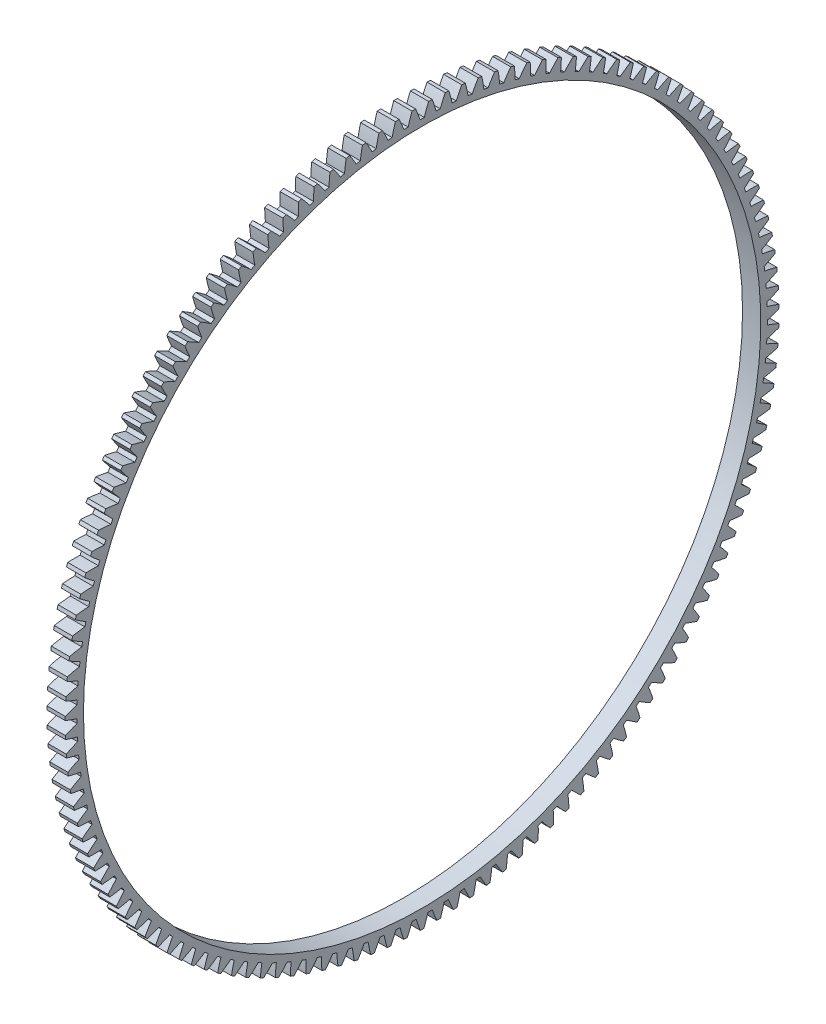
SolidWorks part; units mm, degrees
ref_plane "Plane1" through (0, 0, 0) normal (0, 0, 1) x (1, 0, 0)
ref_plane "Plane2" through (0, 0, 0) normal (0, 1, 0) x (1, 0, 0)
ref_plane "Plane3" through (0, 0, 0) normal (1, 0, 0) x (0, 0, -1)
sketch "HoldingSke" plane through (0, 0, 0) normal (0, 1, 0) x (1, 0, 0)
  line L0 (0, 0) -> (-0.3536, -0.3536)
  line L1 (-15, 0) -> (100, 0) construction
  line L2 (0, 0) -> (-2.1039, 2.3779)
  line L3 (0, 0) -> (-11.863, 4.5341)
  line L4 (0, 0) -> (-6.1066, 6.1066)
  line L5 (0, 0) -> (-46.8476, -17.4728)
  line L6 (0, 0) -> (-7.4607, -5.0337)
  line L7 (-2.1039, 2.3779) -> (8.6586, 51.2059)
  line L8 (-76.2, 54.61) -> (-63.8, 54.61)
  line L9 (-71.009, 38.7566) -> (-53.1078, 45.2721)
  line L10 (-76.2, 71.12) -> (104.1128, 71.12)
  line L11 (0, 0) -> (-9, 0)
  line L12 (-76.2, 101.6) -> (-76.133, 101.6)
  line L13 (24.9733, 27.94) -> (52.9518, 28.4284)
  line L14 (24.9733, 27.94) -> (24.9743, 27.94)
  line L15 (24.9733, 27.94) -> (100.4006, 29.5858)
  line L16 (-63.627, -2) -> (-12.827, -2)
  circle A0 centre (0, 0) radius 130
  circle A1 centre (0, 0) radius 37.5
  circle A2 centre (0, 0) radius 37.5
  circle A3 centre (0, 0) radius 130
  dimension "Num_teeth" = 135
  dimension "Pitch_radius" = 180.3128
  dimension "Width" = 9
sketch "BasProSke" plane through (0, 0, 0) normal (0, 1, 0) x (1, 0, 0)
  line L0 (-10, 0) -> (60, 0) construction
  line L1 (0, 0) -> (0, 137)
  line L2 (0, 0) -> (7, 0)
  line L3 (7, 0) -> (7, 137)
  line L4 (7, 137) -> (0, 137)
  dimension "Thickness" = 7
  dimension "Diameter" = 274
revolve "Base-Revolve" add sketch "BasProSke" angle 360 about L0
sketch "TooCutSke" plane through (0, 0, 0) normal (1, 0, 0) x (0, 0, -1)
  line L1 (0, 0) -> (0, 107) construction
  line L2 (0, 0) -> (-1.688, 134.9894) construction
  line L3 (0, 0) -> (-6.2823, 269.9112) construction
  line L4 (-1.688, 134.9894) -> (-3.1411, 134.9556) construction
  arc A0 (0.8019, 132.4966) -> (-0.8019, 132.4966) centre (0, 0) ccw
  arc A1 (2.5065, 137.0025) -> (-2.5065, 137.0025) centre (0, 0) ccw
  circle A2 centre (0, 0) radius 135 construction
  circle A3 centre (0, 0) radius 126.8585 construction
  arc A4 (-0.8019, 132.4966) -> (-2.5065, 137.0025) centre (-52.1105, 115.6615) ccw
  arc A5 (2.5065, 137.0025) -> (0.8019, 132.4966) centre (52.1105, 115.6615) ccw
extrude "ToothCut" cut sketch "TooCutSke" along normal through all
fillet "Breaks" [suppressed] radius 0.04 tangent propagation no
fillet "RootFillets" [suppressed] radius 0.501
pattern_circular "TeethCuts" count 135 every 2.667 about axis through (-10, 0, 0) along (1, 0, 0) of "ToothCut", "RootFillets", "Breaks"
sketch "HubNeaOneSke" plane through (0, 0, 0) normal (-1, 0, 0) x (0, 0, 1)
  circle A0 centre (0, 0) radius 37.5
  dimension "Diameter" = 75
extrude "HubNearOne" [suppressed] add sketch "HubNeaOneSke" along normal blind 43.0001
sketch "HubNeaBotSke" plane through (0, 0, 0) normal (-1, 0, 0) x (0, 0, 1)
  circle A0 centre (0, 0) radius 37.5
  dimension "Diameter" = 75
extrude "HubNearBoth" [suppressed] add sketch "HubNeaBotSke" along normal blind 21.5
ref_plane "FarPln" through (7, 0, 0) normal (1, 0, 0) x (0, 0, -1)
sketch "HubFarSke" plane through (7, 0, 0) normal (1, 0, 0) x (0, 0, -1)
  circle A0 centre (0, 0) radius 37.5
  dimension "Diameter" = 75
extrude "HubFar" [suppressed] add sketch "HubFarSke" along normal blind 21.5
sketch "BorSke" plane through (0, 0, 0) normal (1, 0, 0) x (0, 0, -1)
  circle A0 centre (0, 0) radius 130
  dimension "Diameter" = 260
extrude "Bore" cut sketch "BorSke" along normal mid plane 100.0001
sketch "KeySke" plane through (0, 0, 0) normal (1, 0, 0) x (0, 0, -1)
  line L0 (-31.5, 0) -> (-31.5, 142.4)
  line L1 (-31.5, 142.4) -> (31.5, 142.4)
  line L2 (31.5, 142.4) -> (31.5, 0)
  line L3 (0, 0) -> (0, 34) construction
  line L4 (-31.5, 0) -> (31.5, 0)
  dimension "Width" = 63
extrude "Keyway" [suppressed] cut sketch "KeySke" along normal mid plane 100.0001
pattern_circular "Keyway2" [suppressed] count 2 every 90 about axis through (-10, 0, 0) along (1, 0, 0) reverse direction yes
ref_axis "Axis1" through (-80.9, 0, 0) along (1, 0, 0)
equation "' \"Module@HoldingSke\" = 6.35"
equation "' \"Num_teeth@HoldingSke\" = 12"
equation "' \"Ap@HoldingSke\" =  20"
equation "' \"Ap@HoldingSke\" = 20"
equation "' \"Width@HoldingSke\" = 0.5 * 25.4"
equation "' \"Hub_dia@HoldingSke\"= 1 * 25.4"
equation "' \"Hub_dia@HoldingSke\" = 1 * 25.4"
equation "' \"Overall_len@HoldingSke\" = 1.0 * 25.4"
equation "' \"Bore@HoldingSke\" = 0.75 * 25.4"
equation "' \"T_dim@HoldingSke\" = 0.1 * 25.4"
equation "' \"Width@KeySke\" = 0.25 * 25.4"
equation "' \"Show_teeth@HoldingSke\" = 13"
equation "' \"Backlash@HoldingSke\" = 0.009 * 25.4"
equation "' \"Addendum_fac@HoldingSke\" = 1.0"
equation "' \"Dedendum_fac@HoldingSke\" = 1.25"
equation "' \"Dedendum_add@HoldingSke\" = 0.00005 * 25.4"
equation "' \"Clearance_fac@HoldingSke\" = 0.25"
equation "\"Pitch@HoldingSke\" = 1 / \"Module@HoldingSke\""
equation "\"Overcut_dia@TooCutSke\" = (\"Num_teeth@HoldingSke\" + 2 * \"Addendum_fac@HoldingSke\") / \"Pitch@HoldingSke\" + 0.002 * 25.4"
equation "\"Pitch_dia@TooCutSke\" = \"Num_teeth@HoldingSke\" / \"Pitch@HoldingSke\""
equation "\"Base_dia@TooCutSke\" = \"Num_teeth@HoldingSke\" / \"Pitch@HoldingSke\" * cos((\"Ap@HoldingSke\"  * 3.14159265 / 180))"
equation "\"Root_dia@TooCutSke\" = (\"Num_teeth@HoldingSke\" + 2) / \"Pitch@HoldingSke\" - 2 * (\"Addendum_fac@HoldingSke\" + \"Dedendum_fac@HoldingSke\") / \"Pitch@HoldingSke\" - \"Dedendum_add@HoldingSke\" * 2"
equation "\"Half_ang@TooCutSke\" = 180 / \"Num_teeth@HoldingSke\""
equation "\"Half_CT@TooCutSke\" = \"Num_teeth@HoldingSke\" / \"Pitch@HoldingSke\" * sin((3.14159265 / 2 / \"Num_teeth@HoldingSke\")) / 2 - 7 * \"Backlash@HoldingSke\" / 4"
equation "\"Flank_rad@TooCutSke\" = \"Num_teeth@HoldingSke\" / \"Pitch@HoldingSke\" / 5"
equation "\"Radius@RootFillets\" = \"Clearance_fac@HoldingSke\" / \"Pitch@HoldingSke\" + \"Dedendum_add@HoldingSke\""
equation "\"Break_rad@Breaks\" = 0.02 / \"Pitch@HoldingSke\""
equation "\"Thickness@HoldingSke\" = \"Width@HoldingSke\""
equation "\"OAL@HoldingSke\" = \"Thickness@HoldingSke\""
equation "\"MHD@HoldingSke\" = (\"Num_teeth@HoldingSke\" + 2) / \"Pitch@HoldingSke\" - 2 * (\"Addendum_fac@HoldingSke\" + \"Dedendum_fac@HoldingSke\")  / \"Pitch@HoldingSke\" - \"Dedendum_add@HoldingSke\" * 2"
equation "\"MBD@HoldingSke\" = (\"Num_teeth@HoldingSke\" + 2) / \"Pitch@HoldingSke\" - 2 * (\"Addendum_fac@HoldingSke\" + \"Dedendum_fac@HoldingSke\")  / \"Pitch@HoldingSke\" - \"Dedendum_add@HoldingSke\" * 2 - 0.002 * 25.4"
equation "\"MHD@HoldingSke\" = ((sgn( \"MHD@HoldingSke\" - \"Hub_dia@HoldingSke\" )-1)*( \"MHD@HoldingSke\" - \"Hub_dia@HoldingSke\" ))/-2+ \"Hub_dia@HoldingSke\""
equation "\"MBD@HoldingSke\" = ((sgn( \"MBD@HoldingSke\" - \"Bore@HoldingSke\" )-1)*( \"MBD@HoldingSke\" - \"Bore@HoldingSke\" ))/-2+ \"Bore@HoldingSke\""
equation "\"OAL@HoldingSke\" = ((sgn( \"OAL@HoldingSke\" - \"Overall_len@HoldingSke\" )+1)*( \"OAL@HoldingSke\" - \"Overall_len@HoldingSke\" ))/2 + \"Overall_len@HoldingSke\" + 0.000002 * 25.4"
equation "\"Num_teeth@TeethCuts\" = int( \"Show_teeth@HoldingSke\" ) + 1"
equation "\"Num_teeth@TeethCuts\" = ((sgn( \"Num_teeth@TeethCuts\" - \"Num_teeth@HoldingSke\" )-1)*( \"Num_teeth@TeethCuts\" - \"Num_teeth@HoldingSke\" ))/-2+ \"Num_teeth@HoldingSke\""
equation "\"Num_teeth@TeethCuts\" = ((sgn( \"Num_teeth@TeethCuts\" - 2.0)+1)*( \"Num_teeth@TeethCuts\" - 2.0))/2 +2.0"
equation "\"Angle@TeethCuts\" = 360.0 / \"Num_teeth@HoldingSke\""
equation "\"Diameter@BasProSke\" = (\"Num_teeth@HoldingSke\" + 2 * \"Addendum_fac@HoldingSke\") / \"Pitch@HoldingSke\""
equation "' \"Fillet_rad@BasProSke\" =  \"Thickness@HoldingSke\" * 0.05"
equation "' \"Fillet_rad@BasProSke\" = \"Thickness@HoldingSke\" * 0.05"
equation "\"MHD@HoldingSke\" = ((sgn( \"MHD@HoldingSke\" - \"Root_dia@TooCutSke\" )-1)*( \"MHD@HoldingSke\" - \"Root_dia@TooCutSke\" ))/-2+ \"Root_dia@TooCutSke\""
equation "\"Diameter@HubNeaOneSke\" = \"MHD@HoldingSke\""
equation "\"Length@HubNearOne\" = \"OAL@HoldingSke\" - \"Thickness@BasProSke\""
equation "\"Diameter@HubNeaBotSke\" = \"MHD@HoldingSke\""
equation "\"Length@HubNearBoth\" = ( \"OAL@HoldingSke\" - \"Thickness@BasProSke\" ) / 2.0"
equation "\"Thickness@FarPln\" = \"Thickness@BasProSke\""
equation "\"Diameter@HubFarSke\" = \"MHD@HoldingSke\""
equation "\"Length@HubFar\" = ( \"OAL@HoldingSke\" - \"Thickness@BasProSke\" ) / 2.0"
equation "\"Diameter@BorSke\" = \"MBD@HoldingSke\""
equation "\"D1@Bore\" = \"OAL@HoldingSke\" * 2.0"
equation "\"D1@Keyway\" = \"OAL@HoldingSke\" * 2.0"
equation "\"Offset@KeySke\" = \"T_dim@HoldingSke\" + \"MBD@HoldingSke\" / 2.0"
